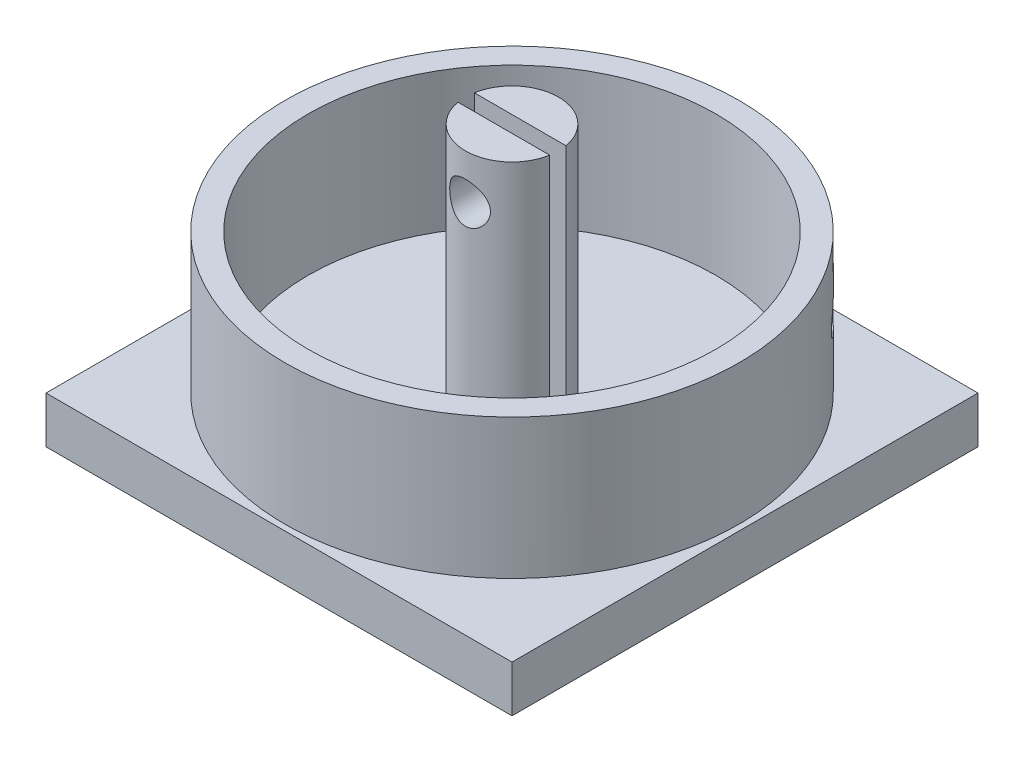
SolidWorks part; units mm, degrees
ref_plane "Front Plane" through (0, 0, 0) normal (0, 0, 1) x (1, 0, 0)
ref_plane "Top Plane" through (0, 0, 0) normal (0, 1, 0) x (1, 0, 0)
ref_plane "Right Plane" through (0, 0, 0) normal (1, 0, 0) x (0, 0, -1)
sketch "Sketch1" plane through (0, 0, 0) normal (0, 1, 0) x (1, 0, 0)
  line L1 (-35.9084, -76.9224) -> (-15.9084, -76.9224)
  line L2 (-35.9084, -76.9224) -> (-35.9084, -96.9224)
  line L3 (-35.9084, -96.9224) -> (-15.9084, -96.9224)
  line L4 (-15.9084, -76.9224) -> (-15.9084, -96.9224)
extrude "Boss-Extrude1" add sketch "Sketch1" along normal blind 2 contours L2 L1 L4 L3
sketch "Sketch2" plane through (0, 2, 0) normal (0, 1, 0) x (1, 0, 0)
  circle A0 centre (-25.9084, -86.9224) radius 8.75
  circle A1 centre (-25.9084, -86.9224) radius 9.75
extrude "Boss-Extrude2" add sketch "Sketch2" along normal blind 6
sketch "Sketch3" plane through (0, 2, 0) normal (0, 1, 0) x (1, 0, 0)
  line L0 (-25.9084, -86.9224) -> (-25.9084, -86.5724)
  line L1 (-25.9084, -86.5724) -> (-28.4846, -86.5724)
  line L3 (-28.4846, -86.5724) -> (-23.2848, -86.5724)
  line L4 (-28.4846, -86.5724) -> (-28.4846, -87.2724)
  line L5 (-28.4846, -87.2724) -> (-23.2848, -87.2724)
  line L6 (-23.2848, -86.5724) -> (-23.2848, -87.2724)
  circle A0 centre (-25.9084, -86.9224) radius 2
extrude "Boss-Extrude3" add sketch "Sketch3" along normal blind 9 contours L3 A0 L1 | L5 A0 region at (-25.9084, 2, 85.8815) region at (-25.9084, 2, 87.9632)
sketch "Sketch4" plane through (0, 0, 86.5724) normal (0, 0, 1) x (1, 0, 0)
  line L0 (-25.9084, 8) -> (-25.9084, 9.2)
  line L1 (-16.1584, 8) -> (-35.6584, 8) construction
  line L2 (-25.9084, 9.2) -> (-26.7834, 9.2)
  line L5 (-25.9084, 9.2) -> (-25.0334, 9.2)
  line L8 (-25.0334, 9.2) -> (-25.0334, 10.95)
  line L9 (-25.0334, 10.95) -> (-26.7834, 10.95)
  line L10 (-26.7834, 10.95) -> (-26.7834, 9.2)
extrude "Cut-Extrude4" cut sketch "Sketch4" against normal blind 6 contours L9 L10 L2 L5 L8 region at (-25.9084, 10.075, 86.5724)
sketch "Sketch6" plane through (0, 0, 87.2724) normal (0, 0, -1) x (-1, 0, 0)
  circle A0 centre (25.9084, 10.075) radius 0.875
extrude "Cut-Extrude5" cut sketch "Sketch6" against normal blind 6
sketch "Sketch7" plane through (0, 11, 0) normal (0, 1, 0) x (1, 0, 0)
  line L0 (-23.9393, -86.5724) -> (-27.8776, -86.5724)
  line L1 (-27.8776, -87.2724) -> (-23.9393, -87.2724)
  circle A0 centre (-25.9084, -86.9224) radius 2
  line M1 (-23.9393, -87.2724) -> (-27.8776, -87.2724)
  arc M2 (-27.8776, -87.2724) -> (-23.9393, -87.2724) centre (-25.9084, -86.9224) ccw
extrude "Boss-Extrude4" add sketch "Sketch7" along normal blind 1 contours L0 A0 | M2 M1 region at (-25.9084, 11, 85.8815) region at (-25.9084, 11, 87.9632)
sketch "Sketch8" plane through (0, 0, 76.9224) normal (0, 0, -1) x (-1, 0, 0)
  line L0 (25.9084, 2) -> (25.9084, 8)
  line L1 (35.9084, 2) -> (15.9084, 2) construction
  line L2 (35.6584, 8) -> (16.1584, 8) construction
  line L3 (25.9084, 5) -> (18.9084, 5)
  circle A0 centre (18.9084, 5) radius 0.6
extrude "Cut-Extrude6" cut sketch "Sketch8" against normal blind 12 contours A0 region at (-18.3254, 5, 76.9224)
